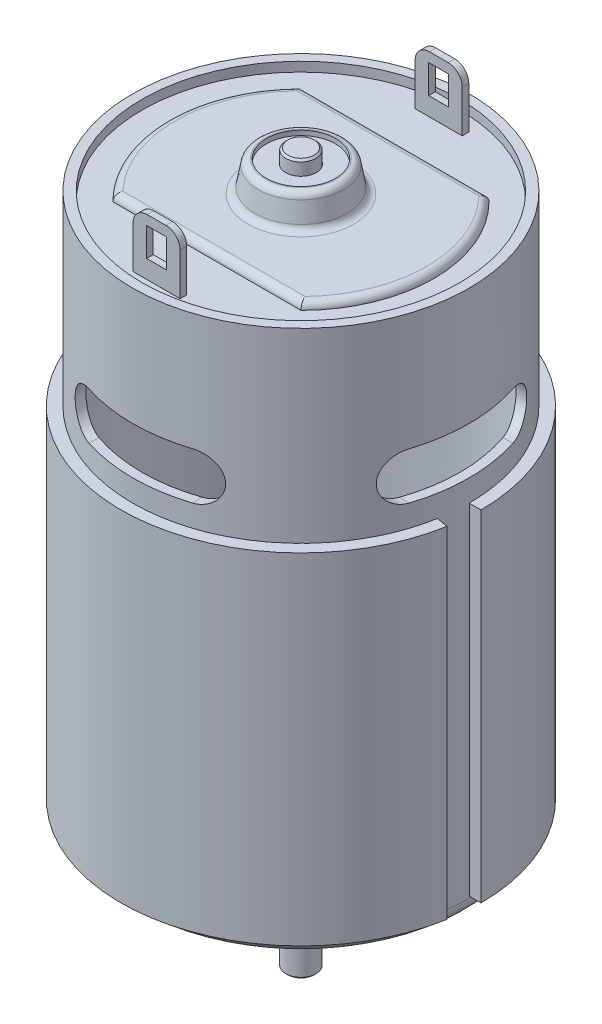
SolidWorks part; units mm, degrees
ref_plane "Front Plane" through (0, 0, 0) normal (0, 0, 1) x (1, 0, 0)
ref_plane "Top Plane" through (0, 0, 0) normal (0, 1, 0) x (1, 0, 0)
ref_plane "Right Plane" through (0, 0, 0) normal (1, 0, 0) x (0, 0, -1)
sketch "Sketch1" plane through (0, 0, 0) normal (0, 1, 0) x (1, 0, 0)
  circle A0 centre (0, 0) radius 17.9
  dimension "D1" = 35.8
extrude "Boss-Extrude1" add sketch "Sketch1" along normal blind 58
sketch "Sketch8" plane through (0, 0, 0) normal (0, 0, 1) x (1, 0, 0)
  line L0 (0, 56) -> (0, 1)
  line L1 (0, 1) -> (16.9, 1)
  line L2 (16.9, 1) -> (16.9, 56)
  line L3 (16.9, 56) -> (0, 56)
  line L4 (17.9, 0) -> (17.9, 40.5282) construction
  line L5 (17.9, 58) -> (-17.9, 58) construction
  line L6 (-17.9, 0) -> (17.9, 0) construction
  dimension "D1" = 1
  dimension "D2" = 2
  dimension "D3" = 1
revolve "Cut-Revolve2" cut sketch "Sketch8" angle 360 about L0
sketch "Sketch2" plane through (0, 0, 0) normal (0, 0, 1) x (1, 0, 0)
  line L0 (-17.9, 0) -> (17.9, 0) construction
  line L1 (17.9, 2) -> (19.15, 2)
  line L2 (17.9, 2) -> (17.9, 38.2)
  line L3 (17.9, 38.2) -> (19.15, 38.2)
  line L4 (19.15, 2) -> (19.15, 38.2)
  line L5 (17.9, 0) -> (17.9, 58) construction
  line L6 (0, 0) -> (0, 58) construction
  line L7 (17.9, 58) -> (-17.9, 58) construction
  dimension "D1" = 36.2
  dimension "D2" = 2
  dimension "D3" = 1.25
revolve "Revolve1" add sketch "Sketch2" angle 350 about L6
sketch "Sketch3" plane through (0, 0, 0) normal (0, -1, 0) x (1, 0, 0)
  circle A0 centre (0, 0) radius 6.5
  dimension "D1" = 13
extrude "Boss-Extrude2" add sketch "Sketch3" along normal blind 4
sketch "Sketch9" plane through (0, 58, 0) normal (0, 1, 0) x (1, 0, 0)
  circle A0 centre (0, 0) radius 16.9
  circle A1 centre (0, 0) radius 17.9 construction
  dimension "D1" = 1
extrude "Cut-Extrude3" cut sketch "Sketch9" against normal blind 1
sketch "Sketch12" plane through (0, 57, 0) normal (0, 1, 0) x (1, 0, 0)
  line L0 (-10, 10) -> (10, 10)
  line L2 (0, 16.9) -> (0, -16.9) construction
  line L3 (-16.9, 0) -> (16.9, 0) construction
  line L4 (-10, -10) -> (10, -10)
  circle A3 centre (0, 0) radius 16.9 construction
  circle A4 centre (0, 0) radius 16.9 construction
  arc A6 (-10, 10) -> (-10, -10) centre (0, 0) ccw
  arc A7 (10, 10) -> (10, -10) centre (0, 0) cw
  point P5 (0, 10)
  dimension "D1" = 20
  dimension "D2" = 20
extrude "Boss-Extrude5" add sketch "Sketch12" along normal blind 0.75
sketch "Sketch13" plane through (0, 57.75, 0) normal (0, 1, 0) x (1, 0, 0)
  circle A0 centre (0, 0) radius 5
  dimension "D1" = 10
extrude "Boss-Extrude6" add sketch "Sketch13" along normal blind 3.25 draft 10
sketch "Sketch14" plane through (0, 57, 0) normal (0, 1, 0) x (1, 0, 0)
  line L0 (-16.9, 0) -> (16.9, 0) construction
  line L1 (2.5, 14.65) -> (-2.5, 14.65)
  line L2 (2.5, 14.65) -> (2.5, 15.35)
  line L3 (2.5, 15.35) -> (-2.5, 15.35)
  line L4 (-2.5, 14.65) -> (-2.5, 15.35)
  line L5 (2.5, 14.65) -> (-2.5, 15.35) construction
  line L6 (2.5, 15.35) -> (-2.5, 14.65) construction
  circle A0 centre (0, 0) radius 16.9 construction
  point P0 (0, 15)
  dimension "D1" = 5
  dimension "D2" = 0.7
  dimension "D3" = 30
extrude "Boss-Extrude7" add sketch "Sketch14" along normal blind 6
sketch "Sketch16" plane through (0, 0, -15.35) normal (0, 0, -1) x (-1, 0, 0)
  line L3 (-1.0634, 61.9679) -> (1.0634, 61.9679)
  line L4 (-1.0634, 61.9679) -> (-1.0634, 58.9272)
  line L5 (-1.0634, 58.9272) -> (1.0634, 58.9272)
  line L6 (1.0634, 61.9679) -> (1.0634, 58.9272)
  point P4 (0, 61.9679)
extrude "Cut-Extrude5" cut sketch "Sketch16" against normal up to surface (0.7 mm away) up to face at (0, 60, -14.65)
mirror "Mirror3" about plane through (0, 0, 0) normal (0, 0, 1) of "Boss-Extrude7", "Cut-Extrude5"
sketch "Sketch5" plane through (0, 0, 0) normal (0, 0, 1) x (1, 0, 0)
  line L0 (-5.5, 45.5282) -> (5.5, 45.5282)
  line L1 (5.5, 40.5282) -> (-5.5, 40.5282)
  line L2 (17.9, 58) -> (-17.9, 58) construction
  arc A0 (5.5, 45.5282) -> (5.5, 40.5282) centre (5.5, 43.0282) cw
  arc A1 (-5.5, 40.5282) -> (-5.5, 45.5282) centre (-5.5, 43.0282) cw
  point P6 (-8, 43.0282)
  point P7 (8, 43.0282)
  point P8 (0, 45.5282)
  dimension "D1" = 5
  dimension "D2" = 16
  dimension "D3" = 12.4718
extrude "Cut-Extrude1" cut sketch "Sketch5" against normal through all both and the other way through all
pattern_circular "CirPattern1" count 2 over 90 about axis through (0, 58, 0) along (0, -1, 0) of "Cut-Extrude1"
sketch "Sketch6" plane through (0, 0, 0) normal (0, -1, 0) x (1, 0, 0)
  line L0 (0, 0) -> (0, 19.15) construction
  line L1 (-5.98, 12.8243) -> (-4.7122, 10.1053)
  line L2 (4.7122, 10.1053) -> (5.98, 12.8243)
  line L3 (10.1053, -4.7122) -> (12.8243, -5.98)
  line L4 (12.8243, 5.98) -> (10.1053, 4.7122)
  line L5 (-4.7122, -10.1053) -> (-5.98, -12.8243)
  line L6 (5.98, -12.8243) -> (4.7122, -10.1053)
  line L7 (-10.1053, 4.7122) -> (-12.8243, 5.98)
  line L8 (-12.8243, -5.98) -> (-10.1053, -4.7122)
  arc A0 (-5.98, 12.8243) -> (5.98, 12.8243) centre (0, 0) cw
  arc A1 (-4.7122, 10.1053) -> (4.7122, 10.1053) centre (0, 0) cw
  arc A3 (-4.7122, 10.1053) -> (4.7122, 10.1053) centre (0, 0) cw construction
  arc A4 (18.8591, 3.3254) -> (19.15, 0) centre (0, 0) ccw construction
  arc A5 (12.8243, 5.98) -> (12.8243, -5.98) centre (0, 0) cw
  arc A6 (10.1053, 4.7122) -> (10.1053, -4.7122) centre (0, 0) cw
  arc A7 (5.98, -12.8243) -> (-5.98, -12.8243) centre (0, 0) cw
  arc A8 (4.7122, -10.1053) -> (-4.7122, -10.1053) centre (0, 0) cw
  arc A9 (-12.8243, -5.98) -> (-12.8243, 5.98) centre (0, 0) cw
  arc A10 (-10.1053, -4.7122) -> (-10.1053, 4.7122) centre (0, 0) cw
  point P11 (0, 11.15)
  point P17 (0, 14.15)
  point P32 (0, 0)
  dimension "D2" = 50
  dimension "D3" = 5
  dimension "D1" = 3
  dimension "D4" = 4
extrude "Cut-Extrude2" cut sketch "Sketch6" against normal blind 20
sketch "Sketch11" plane through (0, 0, 0) normal (0, -1, 0) x (1, 0, 0)
  line L0 (0, 0) -> (9.1924, 9.1924) construction
  line L1 (0, 0) -> (0, 19.15) construction
  circle A0 centre (9.1924, 9.1924) radius 1.5
  arc A1 (18.8591, 3.3254) -> (19.15, 0) centre (0, 0) ccw construction
  circle A2 centre (9.1924, -9.1924) radius 1.5
  circle A3 centre (-9.1924, -9.1924) radius 1.5
  circle A4 centre (-9.1924, 9.1924) radius 1.5
  point P17 (0, 0)
  point P19 (0, 0)
  dimension "D1" = 3
  dimension "D2" = 45
  dimension "D4" = 13
  dimension "D3" = 4
extrude "Cut-Extrude4" cut sketch "Sketch11" against normal up to surface (1 mm away) up to face at (0, 1, 12.0574)
sketch "Sketch17" plane through (0, -4, 0) normal (0, -1, 0) x (1, 0, 0)
  circle A2 centre (0, 0) radius 5.3
  circle A3 centre (0, 0) radius 5.3
  dimension "D1" = 1.2
extrude "Cut-Extrude6" cut sketch "Sketch17" against normal up to surface (5 mm away) up to face at (-10.6924, 1, 9.1924)
sketch "Sketch18" plane through (0, 1, 0) normal (0, 1, 0) x (1, 0, 0)
  circle A2 centre (0, 0) radius 5.3
  circle A3 centre (0, 0) radius 5.3
  dimension "D1" = 0
extrude "Boss-Extrude8" add sketch "Sketch18" against normal blind 4.5 separate body
sketch "Sketch19" plane through (0, 61, 0) normal (0, 1, 0) x (1, 0, 0)
  circle A3 centre (0, 0) radius 3.6769
  circle A4 centre (0, 0) radius 3.6769
  dimension "D1" = 0.75
extrude "Cut-Extrude7" cut sketch "Sketch19" against normal up to surface (5 mm away) up to face at (-16.9, 56, 0)
sketch "Sketch20" plane through (0, 56, 0) normal (0, -1, 0) x (1, 0, 0)
  circle A2 centre (0, 0) radius 3.6769
  circle A3 centre (0, 0) radius 3.6769
  dimension "D1" = 0
extrude "Boss-Extrude9" add sketch "Sketch20" against normal blind 4.5 separate body
sketch "Sketch22" plane through (0, -3.5, 0) normal (0, -1, 0) x (1, 0, 0)
  circle A0 centre (0, 0) radius 1.625
  dimension "D1" = 3.25
extrude "Cut-Extrude8" cut sketch "Sketch22" against normal through all
sketch "Sketch21" plane through (0, -3.5, 0) normal (0, -1, 0) x (1, 0, 0)
  circle A0 centre (0, 0) radius 1.6
  dimension "D1" = 3.2
extrude "Boss-Extrude10" add sketch "Sketch21" along normal blind 10 and the other way blind 65.5 separate body
fillet "Fillet2" radius 1.8 1 edges at (0, 0, 17.9)
fillet "Fillet3" radius 0.75 6 edges at (-9.1924, 0, -10.6924) (9.1924, 0, -10.6924) (9.1924, 0, 7.6924) (-9.1924, 0, 7.6924) (0, 0, -6.5) (0, -4, -6.5)
fillet "Fillet4" radius 0.75 6 edges at (0, 57.75, -10) (14.1421, 57.75, 0) (0, 57.75, 10) (-14.1421, 57.75, 0) (0, 57.75, 5) (0, 61, 4.4269)
fillet "Fillet5" radius 1.5 4 edges at (2.5, 63, 15) (-2.5, 63, 15) (2.5, 63, -15) (-2.5, 63, -15)
chamfer "Chamfer1" distance 0.2 angle 45 2 edges at (1.6, -13.5, 0) (1.6, 62, 0)
chamfer "Chamfer2" distance 0.1 angle 45 1 edges at (1.625, -3.5, 0)
